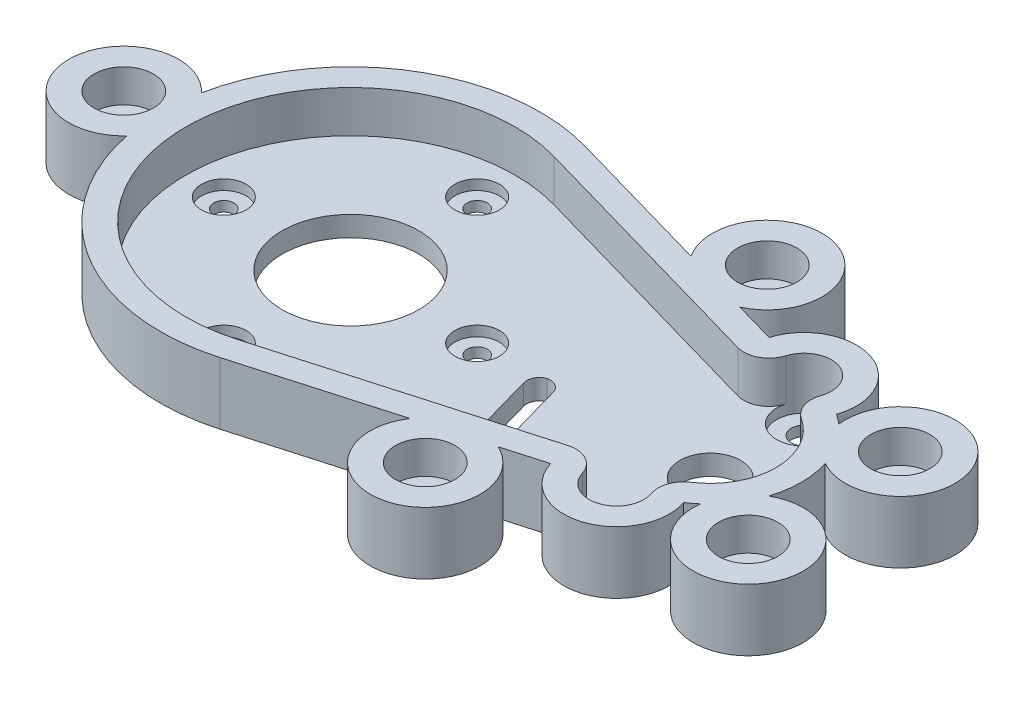
SolidWorks part; units mm, degrees
ref_plane "Front Plane" through (0, 0, 0) normal (0, 0, 1) x (1, 0, 0)
ref_plane "Top Plane" through (0, 0, 0) normal (0, 1, 0) x (1, 0, 0)
ref_plane "Right Plane" through (0, 0, 0) normal (1, 0, 0) x (0, 0, -1)
sketch "Sketch1" plane through (0, 0, 0) normal (0, 1, 0) x (1, 0, 0)
  line L0 (0, 73.0538) -> (0, -65.1274) construction
  line L1 (35.5, 6.365) -> (-28.5632, 24.502) construction
  line L2 (-70.6215, 0) -> (67.3742, 0) construction
  line L3 (35.5, -6.365) -> (-28.5632, -24.502) construction
  line L4 (4.5177, -15.1364) -> (0.1592, 0.2585)
  line L5 (0.1592, 0.2585) -> (4.6815, 1.5388)
  line L6 (4.6815, 1.5388) -> (9.04, -13.8561)
  line L7 (9.04, -13.8561) -> (9.5848, -15.7805)
  line L8 (9.5848, -15.7805) -> (5.0625, -17.0608)
  line L9 (5.0625, -17.0608) -> (4.5177, -15.1364)
  line L10 (-35.5, 0) -> (-60.5, 0) construction
  line L11 (-35.5, 0) -> (-35.5, 25) construction
  line L13 (-100, -75) -> (100, -75)
  line L14 (-100, -75) -> (-100, 75)
  line L15 (-100, 75) -> (100, 75)
  line L16 (100, -75) -> (100, 75)
  line L17 (-100, -75) -> (100, 75) construction
  line L18 (-100, 75) -> (100, -75) construction
  circle A0 centre (35.5, 0) radius 6
  circle A1 centre (-35.5, 0) radius 13.5
  circle A2 centre (-35.5, 0) radius 25.465 construction
  circle A3 centre (35.5, 0) radius 6.365 construction
  circle A4 centre (-60.5, 0) radius 2
  circle A5 centre (-35.5, 25) radius 2
  circle A6 centre (-10.5, 0) radius 2
  circle A7 centre (-35.5, -25) radius 2
  circle A8 centre (35.5, 18.5) radius 2.5
  circle A9 centre (35.5, -18.5) radius 2.5
  point P35 (0, 0)
  dimension "D1" = 12
  dimension "D2" = 27
  dimension "D5" = 50.93
  dimension "D6" = 12.73
  dimension "D12" = 4
  dimension "D19" = 5
  dimension "D3" = 71
  dimension "D4" = 35.5
  dimension "D7" = 90
  dimension "D8" = 27.5
  dimension "D9" = 4.7
  dimension "D10" = 16
  dimension "D11" = 2
  dimension "D13" = 25
  dimension "D15" = 90
  dimension "D16" = 25
  dimension "D17" = 200
  dimension "D18" = 150
  dimension "D20" = 18.5
  dimension "D14" = 4
extrude "Boss-Extrude1" add sketch "Sketch1" along normal blind 4
sketch "Sketch3" plane through (0, 4, 0) normal (0, 1, 0) x (1, 0, 0)
  line L0 (-26.5739, 31.2502) -> (39.0704, 12.5001)
  line L1 (-100, -75) -> (100, -75)
  line L2 (-100, -75) -> (-100, 75)
  line L3 (-100, 75) -> (100, 75)
  line L4 (100, -75) -> (100, 75)
  line L5 (-35.5, 0) -> (35.5, 0) construction
  line L6 (-26.5739, -31.2502) -> (39.0704, -12.5001)
  arc A0 (-26.5739, 31.2502) -> (-26.5739, -31.2502) centre (-35.5, 0) ccw
  arc A1 (39.0704, -12.5001) -> (39.0704, 12.5001) centre (35.5, 0) ccw
  dimension "D1" = 65
  dimension "D2" = 26
extrude "Boss-Extrude2" add sketch "Sketch3" along normal blind 8.25
sketch "Sketch6" plane through (0, 12.25, 0) normal (0, 1, 0) x (1, 0, 0)
  circle A0 centre (35.5, 18.5) radius 5.4
  circle A1 centre (35.5, -18.5) radius 5.4
  dimension "D1" = 10.8
extrude "Cut-Extrude2" cut sketch "Sketch6" against normal up to surface (8.25 mm away) up to face at (-35.5, 4, 27)
fillet "Fillet1" radius 2.5 4 edges at (9.5848, 2, 15.7805) (5.0625, 2, 17.0608) (4.6815, 2, -1.5388) (0.1592, 2, -0.2585)
fillet "Fillet2" radius 5 4 edges at (36.5847, 8.125, 13.2101) (31.7849, 8.125, 14.5811) (36.5847, 8.125, -13.2101) (31.7849, 8.125, -14.5811)
sketch "Sketch2" plane through (0, 4, 0) normal (0, 1, 0) x (1, 0, 0)
  line L0 (29.5, 0) -> (41.5, 0) construction
  line L1 (35.5, 0) -> (35.5, -6) construction
  line L2 (35.5, 0) -> (35.5, 6) construction
  circle A0 centre (-35.5, 25) radius 4.4
  circle A1 centre (-10.5, 0) radius 4.4
  circle A2 centre (-35.5, -25) radius 4.4
  circle A3 centre (-60.5, 0) radius 4.4
  circle A4 centre (35.5, 0) radius 6 construction
  circle A7 centre (35.5, 18.5) radius 5.4
  circle A8 centre (35.5, -18.5) radius 5.4
  arc A9 (40.6003, 16.7261) -> (30.3389, 20.0883) centre (35.5, 18.5) ccw construction
  dimension "D1" = 8.8
extrude "Cut-Extrude1" cut sketch "Sketch2" against normal blind 2
sketch "Sketch8" plane through (0, 0, 0) normal (0, -1, 0) x (1, 0, 0)
  line L0 (-35.5, 0) -> (-100, 0) construction
  line L1 (-100, -75) -> (-100, 75) construction
  line L2 (-35.5, 0) -> (100, 0) construction
  line L3 (100, 75) -> (100, -75) construction
  line L4 (58, 21) -> (58, -21) construction
  line L5 (13, 32.8542) -> (13, -34.16) construction
  circle A0 centre (-35.5, 0) radius 32.5 construction
  arc A1 (-26.5739, 31.2502) -> (-26.5739, -31.2502) centre (-35.5, 0) ccw construction
  circle A2 centre (-80.25, 0) radius 3
  circle A3 centre (-80.25, 0) radius 5.85 construction
  circle A4 centre (35.5, 0) radius 13.25 construction
  circle A5 centre (58, 15) radius 3
  circle A6 centre (58, 15) radius 5.85 construction
  circle A7 centre (58, -15) radius 5.85 construction
  circle A8 centre (58, -15) radius 3
  circle A9 centre (13, 33.75) radius 3
  circle A10 centre (13, 33.75) radius 5.85 construction
  circle A11 centre (13, -33.75) radius 3
  circle A12 centre (13, -33.75) radius 5.85 construction
  point P11 (-67.75, 0)
  dimension "D1" = 6
  dimension "D2" = 11.7
  dimension "D4" = 26.5
  dimension "D5" = 22.5
  dimension "D3" = 12.5
  dimension "D6" = 30
  dimension "D7" = 22.5
  dimension "D8" = 67.5
extrude "Cut-Extrude3" cut sketch "Sketch8" against normal through all both and the other way through all
sketch "Sketch9" plane through (0, 12.25, 0) normal (0, 1, 0) x (1, 0, 0)
  circle A0 centre (13, 33.75) radius 5.85
  circle A1 centre (58, 15) radius 5.85
  circle A2 centre (58, -15) radius 5.85
  circle A3 centre (13, -33.75) radius 5.85
  circle A4 centre (-80.25, 0) radius 5.85
  dimension "D1" = 11.7
extrude "Cut-Extrude4" cut sketch "Sketch9" against normal blind 6.5
sketch "Sketch12" plane through (0, 12.25, 0) normal (0, 1, 0) x (1, 0, 0)
  line L0 (-100, 0) -> (100, 0) construction
  line L1 (-100, 75) -> (-100, -75) construction
  line L2 (100, -75) -> (100, 75) construction
  line L5 (3.9774, 27.7237) -> (-25.2007, 36.0579)
  line L6 (17.4785, -23.8674) -> (25.5601, -21.559)
  line L7 (25.5601, 21.559) -> (-25.2007, 36.0579)
  line L8 (-25.2007, -36.0579) -> (25.5601, -21.559)
  line L9 (25.5601, 21.559) -> (17.4785, 23.8674)
  line L10 (-25.2007, -36.0579) -> (3.9774, -27.7237)
  arc A0 (17.4785, 23.8674) -> (3.9774, 27.7237) centre (13, 33.75) ccw
  arc A1 (52.6126, 5.582) -> (47.2344, 13.6493) centre (58, 15) ccw
  arc A2 (-72.272, 7.3535) -> (-72.272, -7.3535) centre (-80.25, 0) ccw
  arc A3 (52.6126, -5.582) -> (47.2344, -13.6493) centre (58, -15) cw
  arc A4 (17.4785, -23.8674) -> (3.9774, -27.7237) centre (13, -33.75) cw
  arc A13 (47.2344, 13.6493) -> (45.3228, 15.0835) centre (35.5, 0) ccw
  arc A14 (52.6126, -5.582) -> (52.6126, 5.582) centre (35.5, 0) ccw
  arc A15 (-72.272, -7.3535) -> (-25.2007, -36.0579) centre (-35.5, 0) ccw
  arc A21 (-25.2007, 36.0579) -> (-25.2007, -36.0579) centre (-35.5, 0) ccw
  arc A22 (25.5601, -21.559) -> (45.3228, -15.0835) centre (35.5, -18.5) ccw
  arc A23 (45.3228, -15.0835) -> (45.3228, 15.0835) centre (35.5, 0) ccw
  arc A24 (45.3228, 15.0835) -> (25.5601, 21.559) centre (35.5, 18.5) ccw
  arc A25 (-25.2007, 36.0579) -> (-72.272, 7.3535) centre (-35.5, 0) ccw
  arc A26 (25.5601, -21.559) -> (45.3228, -15.0835) centre (35.5, -18.5) ccw
  arc A27 (45.3228, -15.0835) -> (47.2344, -13.6493) centre (35.5, 0) ccw
  arc A28 (45.3228, 15.0835) -> (25.5601, 21.559) centre (35.5, 18.5) ccw
  dimension "D1" = 21.7
  dimension "D2" = 5
extrude "Cut-Extrude5" cut sketch "Sketch12" against normal through all both and the other way through all flip side to cut
